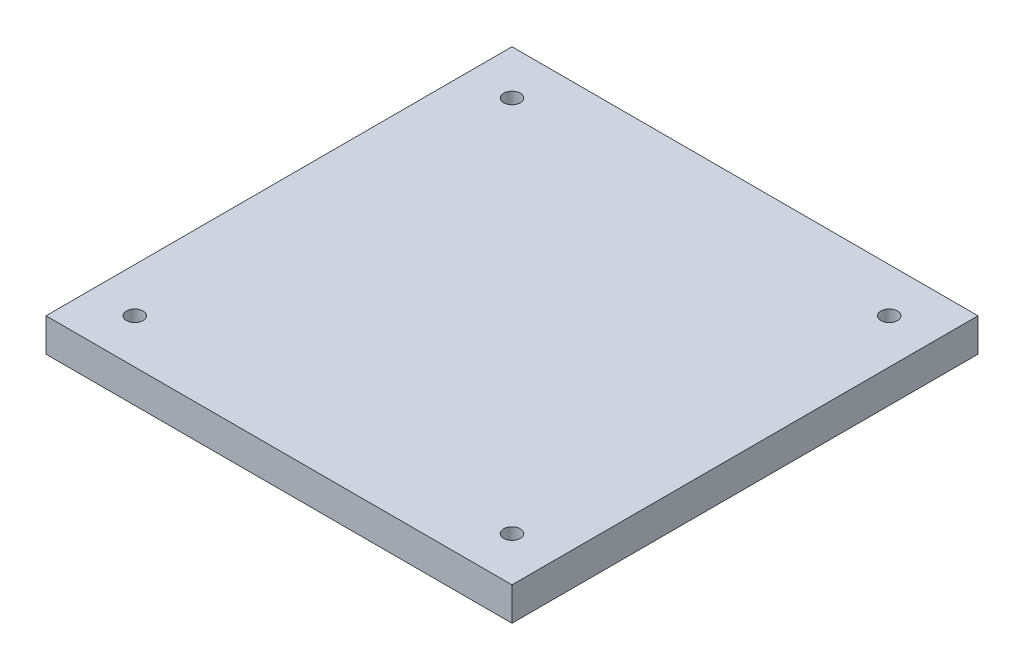
SolidWorks part; units mm, degrees
ref_plane "Front Plane" through (0, 0, 0) normal (0, 0, 1) x (1, 0, 0)
ref_plane "Top Plane" through (0, 0, 0) normal (0, 1, 0) x (1, 0, 0)
ref_plane "Right Plane" through (0, 0, 0) normal (1, 0, 0) x (0, 0, -1)
sketch "Sketch1" plane through (0, 0, 0) normal (0, 1, 0) x (1, 0, 0)
  line L1 (0, 0) -> (84, 0)
  line L2 (0, 0) -> (0, 84)
  line L3 (0, 84) -> (84, 84)
  line L4 (84, 0) -> (84, 84)
  dimension "D1" = 84
  dimension "D2" = 84
extrude "Boss-Extrude1" add sketch "Sketch1" along normal blind 6
sketch "Sketch2" plane through (0, 6, 0) normal (0, 1, 0) x (1, 0, 0)
  line L0 (84, 84) -> (0, 84) construction
  line L1 (0, 84) -> (0, 0) construction
  circle A0 centre (8, 76) radius 1.5
  dimension "D1" = 3
  dimension "D3" = 8
  dimension "D2" = 8
extrude "Cut-Extrude1" cut sketch "Sketch2" against normal blind 6
pattern_linear "LPattern1" count 2 spacing 68 along (1, 0, 0) count 2 spacing 68 along (0, 0, 1) of "Cut-Extrude1"
